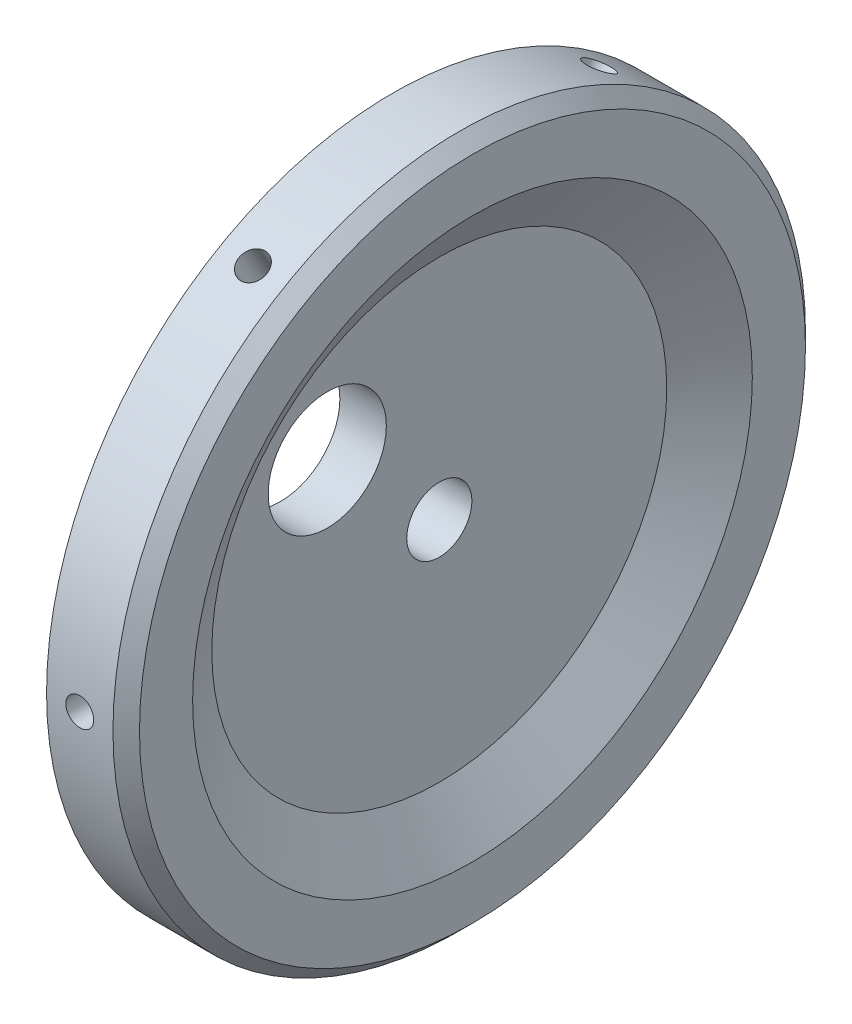
SolidWorks part; units mm, degrees
ref_plane "Front Plane" through (0, 0, 0) normal (0, 0, 1) x (1, 0, 0)
ref_plane "Top Plane" through (0, 0, 0) normal (0, 1, 0) x (1, 0, 0)
ref_plane "Right Plane" through (0, 0, 0) normal (1, 0, 0) x (0, 0, -1)
sketch "Sketch1" plane through (0, 0, 0) normal (0, 1, 0) x (1, 0, 0)
  line L1 (0, -55) -> (0, 55) construction
  line L2 (0, 4.9022) -> (0, 52.15)
  line L3 (0, 52.15) -> (12, 52.15)
  line L4 (12, 52.15) -> (12, 42.15)
  line L8 (7, 4.9022) -> (7, 34.26)
  line L9 (7, 34.26) -> (12, 42.15)
  line L10 (0, 4.9022) -> (7, 4.9022)
  dimension "D2" = 47.2478
  dimension "D3" = 12
  dimension "D4" = 10
  dimension "D6" = 29.3578
sketch "Sketch2" plane through (0, 0, 0) normal (0, 1, 0) x (1, 0, 0)
  line L0 (0, 0) -> (9.8109, 0)
  line L1 (-5.5, 0) -> (5.5, 0) construction
revolve "Revolve1" add sketch "Sketch1" angle 360 about L0
chamfer "Chamfer1" distance 2 angle 45 1 edges at (12, 0, 52.15)
sketch "Sketch3" plane through (7, 0, 0) normal (1, 0, 0) x (0, 0, -1)
  circle A0 centre (-16.8752, 16.2253) radius 8.9
extrude "Cut-Extrude1" cut sketch "Sketch3" against normal blind 10
ref_plane "Plane1" through (0, 0, 52.15) normal (0, 0, 1) x (1, 0, 0)
sketch "Sketch4" plane through (0, 0, 52.15) normal (0, 0, 1) x (1, 0, 0)
  line L0 (12, 0) -> (5, 0)
  line L1 (12, -50.15) -> (12, 50.15) construction
  line L2 (6.6, 0) -> (-6.6, 0) construction
  dimension "D1" = 7
hole_wizard "M5x0.8 Tapped Hole1" positions "Sketch5" profile "Sketch6" tap size "M5x0.8" standard "ANSI Metric"
sketch "Sketch5" plane through (0, 0, 52.15) normal (0, 0, 1) x (1, 0, 0)
  point P0 (5, 0)
sketch "Sketch6" plane through (5, 0, 52.15) normal (1, 0, 0) x (0, -1, 0)
  line L0 (0, 0) -> (0, 10.2618)
  line L1 (0, 10.2618) -> (2.1, 9)
  line L2 (2.1, 9) -> (2.1, 0)
  line L5 (2.1, 0) -> (0, 0)
  line L10 (0, 10.2618) -> (-2.1, 9) construction
  line L11 (0, -6.35) -> (0, 107.95) construction
  dimension "Tap Drill Dia." = 4.2
  dimension "Tap Drill Depth" = 9
  dimension "Drill Angle" = 118
cosmetic thread "Hole Thread1" parameters "D1"=9, "D2"=5
pattern_circular "CirPattern1" count 6 over 360 of "M5x0.8 Tapped Hole1"
cosmetic thread "Hole Thread2" parameters "D1"=9, "D2"=5
cosmetic thread "Hole Thread3" parameters "D1"=9, "D2"=5
cosmetic thread "Hole Thread4" parameters "D1"=9, "D2"=5
cosmetic thread "Hole Thread5" parameters "D1"=9, "D2"=5
cosmetic thread "Hole Thread6" parameters "D1"=9, "D2"=5
